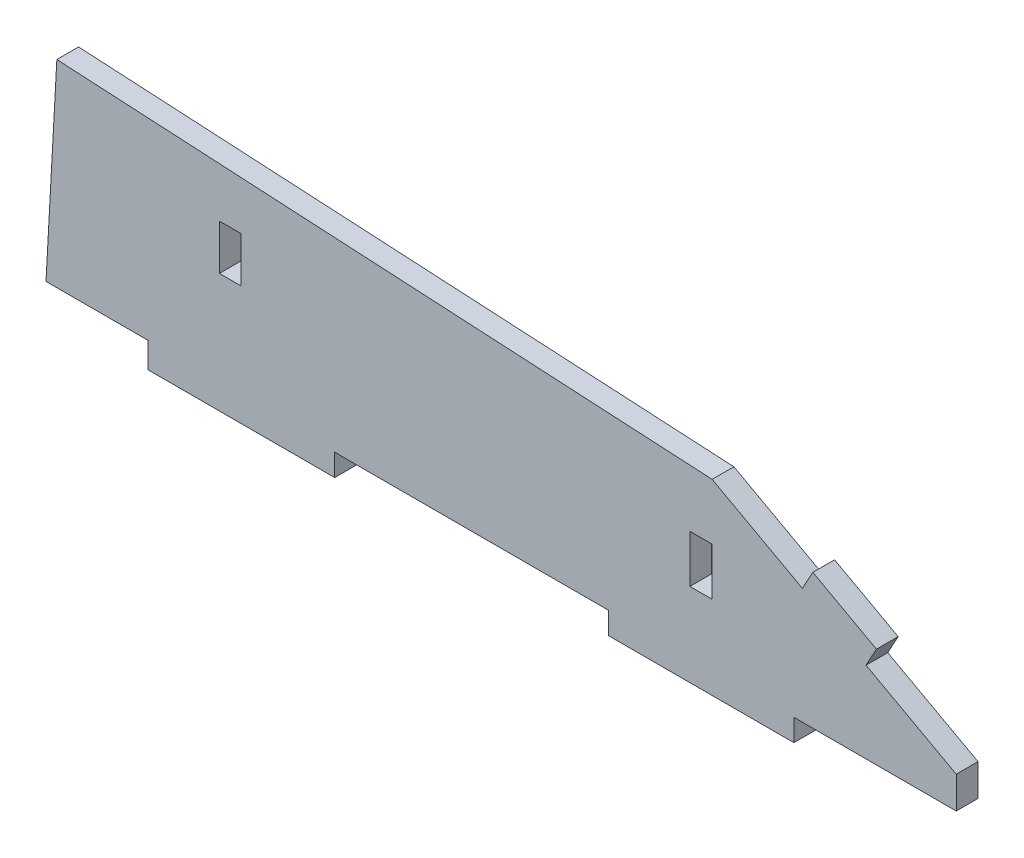
SolidWorks part; units mm, degrees
ref_plane "Front Plane" through (0, 0, 0) normal (0, 0, 1) x (1, 0, 0)
ref_plane "Top Plane" through (0, 0, 0) normal (0, 1, 0) x (1, 0, 0)
ref_plane "Right Plane" through (0, 0, 0) normal (1, 0, 0) x (0, 0, -1)
sketch "Sketch1" plane through (0, 0, 0) normal (0, 0, 1) x (1, 0, 0)
  line L0 (-1.524, -7.3636) -> (-13.6776, -7.3636)
  line L1 (-13.6776, -7.3636) -> (-12.9177, 6.4888)
  line L2 (-6.5267, -7.3636) -> (-6.5267, -9.151)
  line L3 (-6.5267, -9.151) -> (6.5578, -9.151)
  line L4 (6.5578, -9.151) -> (6.5578, -7.6104)
  line L5 (6.5578, -7.6104) -> (25.7442, -7.6104)
  line L6 (25.7442, -7.6104) -> (25.7442, -9.151)
  line L7 (25.7442, -9.151) -> (38.7423, -9.151)
  line L8 (38.7423, -9.151) -> (38.7423, -7.6104)
  line L9 (38.7423, -7.6104) -> (50.1231, -7.6104)
  line L10 (50.1231, -7.6104) -> (50.1231, -5.3731)
  line L11 (50.1231, -5.3731) -> (43.7978, -1.9193)
  line L12 (33.0139, 3.969) -> (-12.9177, 6.4888)
  line L13 (0, 2.376) -> (0, 5.5848) construction
  line L14 (0, 2.376) -> (-1.524, 2.376)
  line L15 (0, 2.376) -> (0, -0.7991)
  line L16 (0, -0.7991) -> (-1.524, -0.7991)
  line L17 (-1.524, 2.376) -> (-1.524, -0.7991)
  line L18 (-1.524, 2.376) -> (0, 2.376) construction
  line L19 (39.3392, 0.5152) -> (33.0139, 3.969)
  line L20 (33.0139, 0.0357) -> (31.4497, 0.0357)
  line L21 (33.0139, 0.0357) -> (33.0139, -3.3106)
  line L22 (33.0139, -3.3106) -> (31.4497, -3.3106)
  line L23 (31.4497, 0.0357) -> (31.4497, -3.3106)
  line L24 (43.7978, -1.9193) -> (44.5282, -0.5817)
  line L25 (39.3392, 0.5152) -> (40.0695, 1.8528)
  line L27 (44.5282, -0.5817) -> (40.0695, 1.8528)
extrude "Boss-Extrude1" add sketch "Sketch1" along normal blind 1.524 contours L11 L12 L1 L0 L2 L3 L4 L5 L6 L7 L8 L9 L10 L23 L20 L21 L22 L17 L14 L15 L16 region at (14.57, -1.9401, 0)
